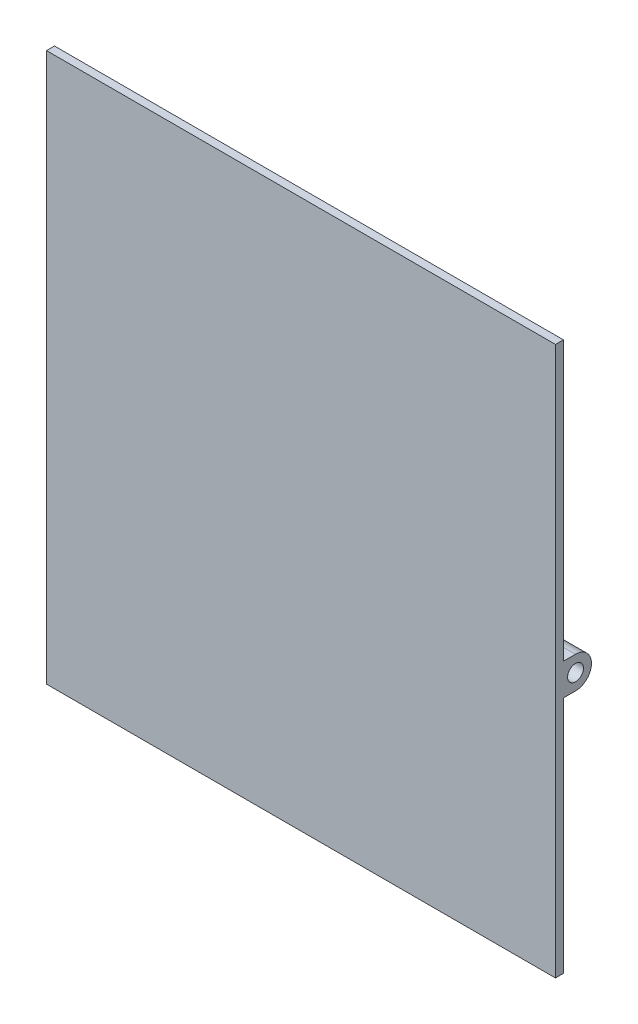
SolidWorks part; units mm, degrees
ref_plane "Płaszczyzna przednia" through (0, 0, 0) normal (0, 0, 1) x (1, 0, 0)
ref_plane "Płaszczyzna górna" through (0, 0, 0) normal (0, 1, 0) x (1, 0, 0)
ref_plane "Płaszczyzna prawa" through (0, 0, 0) normal (1, 0, 0) x (0, 0, -1)
sketch "Szkic1" plane through (0, 0, 0) normal (0, 0, 1) x (1, 0, 0)
  line L0 (0, -69) -> (128, -69) construction
  line L1 (0, 0) -> (128, 0)
  line L2 (0, 0) -> (0, -138)
  line L3 (0, -138) -> (128, -138)
  line L4 (128, 0) -> (128, -138)
  dimension "D1" = 128
  dimension "D2" = 138
extrude "Dodanie-wyciągnięcie1" add sketch "Szkic1" along normal blind 2
sketch "Szkic3" plane through (128, 0, 0) normal (1, 0, 0) x (0, 0, -1)
  line L0 (0, -138) -> (0, 0) construction
  line L1 (0, -70) -> (3.0506, -70)
  line L2 (0, -70) -> (0, -78)
  line L3 (0, -78) -> (3.0506, -78)
  line L6 (-2, -138) -> (0, -138) construction
  arc A0 (3.0506, -78) -> (3.0506, -70) centre (3.0506, -74) ccw
  dimension "D1" = 8
  dimension "D2" = 60
extrude "Dodanie-wyciągnięcie2" add sketch "Szkic3" against normal up to surface (128 mm away) up to face at (0, -69, 1)
sketch "Szkic5" plane through (128, 0, 0) normal (1, 0, 0) x (0, 0, -1)
  circle A0 centre (3.0506, -74) radius 2
  arc A1 (3.0506, -78) -> (3.0506, -70) centre (3.0506, -74) ccw construction
  dimension "D1" = 4
extrude "Wytnij-wyciągnięcie1" cut sketch "Szkic5" against normal through all
